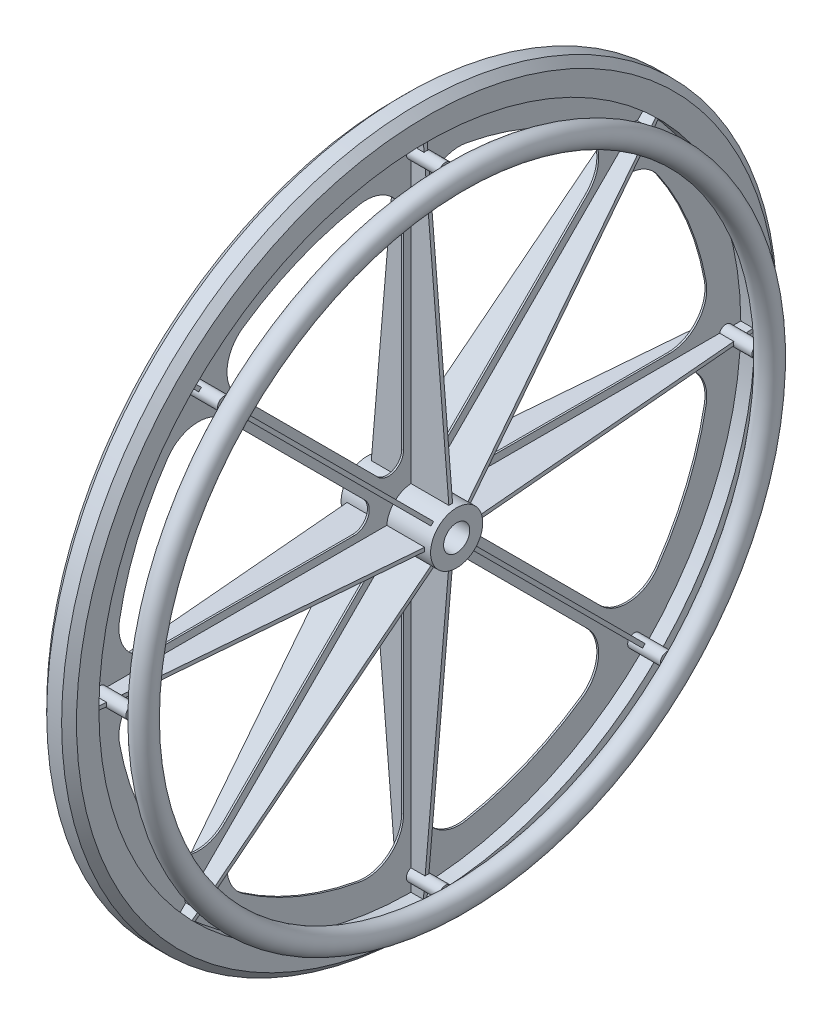
SolidWorks part; units mm, degrees
ref_plane "Front Plane" through (0, 0, 0) normal (0, 0, 1) x (1, 0, 0)
ref_plane "Top Plane" through (0, 0, 0) normal (0, 1, 0) x (1, 0, 0)
ref_plane "Right Plane" through (0, 0, 0) normal (1, 0, 0) x (0, 0, -1)
sketch "Sketch1" plane through (0, 0, 0) normal (1, 0, 0) x (0, 0, -1)
  circle A0 centre (0, 0) radius 22.225
  dimension "D2" = 44.45
extrude "Boss-Extrude1" add sketch "Sketch1" along normal blind 38.1 and the other way blind 38.1
sketch "Sketch2" plane through (0, 0, 0) normal (1, 0, 0) x (0, 0, -1)
  circle A0 centre (0, 0) radius 304.8
  dimension "D1" = 609.6
extrude "Boss-Extrude2" add sketch "Sketch2" along normal blind 0.762 and the other way blind 0.762
sketch "Sketch3" plane through (0, 0, 0) normal (1, 0, 0) x (0, 0, -1)
  circle A0 centre (0, 0) radius 304.8 construction
  circle A1 centre (0, 0) radius 304.8
  circle A2 centre (0, 0) radius 279.4
  dimension "D1" = 25.4
extrude "Boss-Extrude3" add sketch "Sketch3" along normal blind 12.7 and the other way blind 12.7
sketch "Sketch4" plane through (0, 0, 0) normal (1, 0, 0) x (0, 0, -1)
  line L0 (0, 304.8) -> (0, -304.8) construction
  line L1 (-304.8, 0) -> (304.8, 0) construction
  line L2 (-215.5261, -215.5261) -> (215.5261, 215.5261) construction
  line L3 (-215.5261, 215.5261) -> (215.5261, -215.5261) construction
  line L4 (149.0159, 160.2412) -> (29.6178, 40.8431)
  line L5 (7.9375, 218.6778) -> (7.9375, 49.8233)
  circle A0 centre (0, 0) radius 304.8 construction
  circle A1 centre (0, 0) radius 304.8 construction
  arc A2 (45.3571, 249.9174) -> (144.646, 208.7907) centre (0, 0) cw
  arc A3 (29.6178, 40.8431) -> (7.9375, 49.8233) centre (20.6375, 49.8233) cw
  arc A4 (144.646, 208.7907) -> (149.0159, 160.2412) centre (126.5652, 182.6918) cw
  arc A5 (45.3571, 249.9174) -> (7.9375, 218.6778) centre (39.6875, 218.6778) ccw
  dimension "D4" = 50.8
  dimension "D5" = 12.7
  dimension "D6" = 31.75
  dimension "D1" = 45
  dimension "D2" = 15.875
  dimension "D3" = 15.875
extrude "Cut-Extrude1" cut sketch "Sketch4" against normal through all and the other way through all
sketch "Sketch5" plane through (0, 0, 0) normal (0, 1, 0) x (1, 0, 0)
  line L1 (-34.925, -1.5875) -> (34.925, -1.5875)
  line L2 (-34.925, -1.5875) -> (-34.925, 1.5875)
  line L3 (-34.925, 1.5875) -> (34.925, 1.5875)
  line L4 (34.925, -1.5875) -> (34.925, 1.5875)
  line L5 (-34.925, -1.5875) -> (34.925, 1.5875) construction
  line L6 (-34.925, 1.5875) -> (34.925, -1.5875) construction
  line L7 (38.1, -22.225) -> (38.1, 22.225) construction
  point P0 (0, 0)
  dimension "D1" = 3.175
  dimension "D2" = 3.175
ref_plane "Plane1" through (0, 281.94, 0) normal (0, 1, 0) x (-1, 0, 0)
sketch "Sketch6" plane through (0, 281.94, 0) normal (0, 1, 0) x (-1, 0, 0)
  line L1 (11.1125, 1.5875) -> (-11.1125, 1.5875)
  line L2 (11.1125, 1.5875) -> (11.1125, -1.5875)
  line L3 (11.1125, -1.5875) -> (-11.1125, -1.5875)
  line L4 (-11.1125, 1.5875) -> (-11.1125, -1.5875)
  line L5 (11.1125, 1.5875) -> (-11.1125, -1.5875) construction
  line L6 (11.1125, -1.5875) -> (-11.1125, 1.5875) construction
  point P0 (0, 0)
  dimension "D1" = 22.225
  dimension "D2" = 3.175
loft "Loft1" add profiles "Sketch5", "Sketch6" connector at (-34.925, 0, 1.5875) connector at (-11.1125, 281.94, 1.5875)
sketch "Sketch7" plane through (0, 0, 0) normal (1, 0, 0) x (0, 0, -1)
  line L0 (0, 266.7) -> (0, 0) construction
  circle A0 centre (0, 266.7) radius 5.5563
  dimension "D2" = 11.1125
  dimension "D1" = 266.7
extrude "Boss-Extrude5" add sketch "Sketch7" along normal blind 28.575
pattern_circular "CirPattern1" count 8 over 360 about axis through (-38.1, 0, 0) along (1, 0, 0) of "Cut-Extrude1", "Loft1", "Boss-Extrude5"
sketch "Sketch9" plane through (0, 0, 0) normal (1, 0, 0) x (0, 0, -1)
  circle A0 centre (0, 0) radius 11.1125
  dimension "D1" = 22.225
extrude "Cut-Extrude2" cut sketch "Sketch9" against normal through all and the other way through all
sketch "Sketch8" plane through (0, 0, 0) normal (0, 0, 1) x (1, 0, 0)
  line L0 (28.575, 261.1438) -> (28.575, 272.2562) construction
  line L1 (28.575, 261.1438) -> (28.575, 272.2562) construction
  line L2 (28.575, 266.7) -> (38.1, 266.7) construction
  circle A0 centre (38.1, 266.7) radius 9.525
  dimension "D1" = 19.05
revolve "Revolve1" add sketch "Sketch8" angle 360 about axis through (-38.1, 0, 0) along (1, 0, 0)
chamfer "Chamfer1" distance 6.35 angle 45 2 edges at (-12.7, 0, -304.8) (12.7, 0, -304.8)
